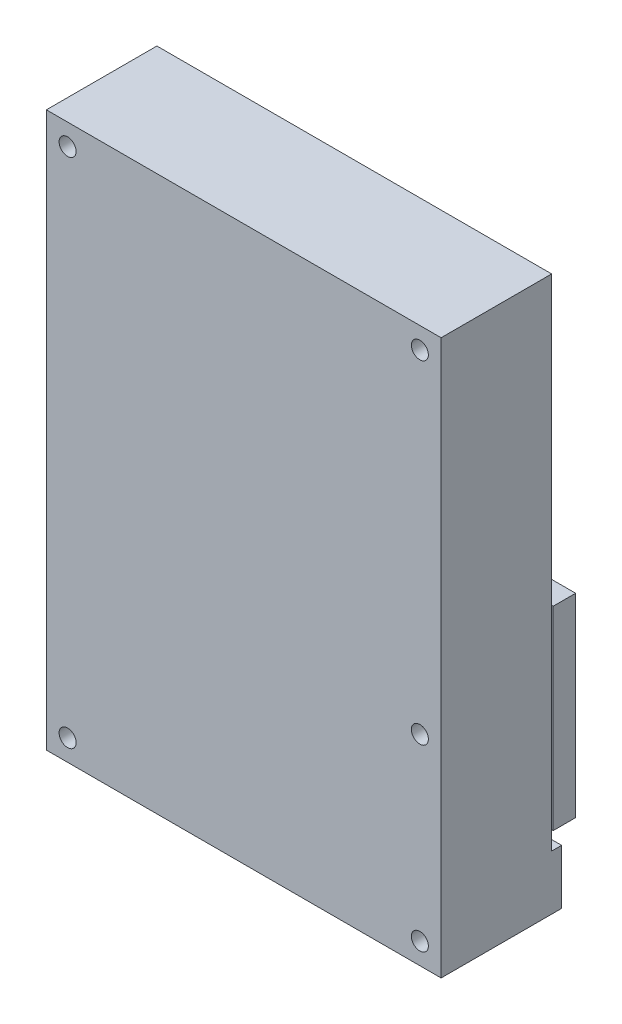
SolidWorks part; units mm, degrees
material "PCB"
ref_plane "Front Plane" through (0, 0, 0) normal (0, 0, 1) x (1, 0, 0)
ref_plane "Top Plane" through (0, 0, 0) normal (0, 1, 0) x (1, 0, 0)
ref_plane "Right Plane" through (0, 0, 0) normal (1, 0, 0) x (0, 0, -1)
sketch "Sketch1" plane through (0, 0, 0) normal (0, 0, 1) x (1, 0, 0)
  line L1 (-30.6623, 34.8708) -> (34.3377, 34.8708)
  line L2 (-30.6623, 34.8708) -> (-30.6623, -56.4292)
  line L3 (-30.6623, -56.4292) -> (34.3377, -56.4292)
  line L4 (34.3377, 34.8708) -> (34.3377, -56.4292)
  dimension "D1" = 65
  dimension "D2" = 91.3
extrude "Boss-Extrude2" add sketch "Sketch1" along normal blind 18.2
sketch "Sketch7" plane through (0, 0, 0) normal (0, 0, -1) x (-1, 0, 0)
  line L0 (-34.3377, -56.4292) -> (-34.3377, 34.8708) construction
  line L1 (30.6623, -56.4292) -> (-34.3377, -56.4292)
  line L2 (30.6623, -56.4292) -> (30.6623, -47.4292)
  line L3 (30.6623, -47.4292) -> (-34.3377, -47.4292)
  line L4 (-34.3377, -56.4292) -> (-34.3377, -47.4292)
  dimension "D1" = 9
sketch "Sketch12" plane through (0, 0, 0) normal (0, 0, -1) x (-1, 0, 0)
  line L1 (-34.3377, -56.4292) -> (30.6623, -56.4292)
  line L2 (-34.3377, -56.4292) -> (-34.3377, -47.4292)
  line L3 (-34.3377, -47.4292) -> (30.6623, -47.4292)
  line L4 (30.6623, -56.4292) -> (30.6623, -47.4292)
extrude "Boss-Extrude7" add sketch "Sketch12" along normal blind 1.64
sketch "Sketch13" plane through (0, -56.4292, 0) normal (0, -1, 0) x (1, 0, 0)
  line L0 (-30.6623, 18.2) -> (-30.6623, -1.64) construction
  line L1 (15.4377, 3.2) -> (-18.7623, 3.2)
  line L2 (15.4377, 3.2) -> (15.4377, 2.95)
  line L3 (15.4377, 2.95) -> (-18.7623, 2.95)
  line L4 (-18.7623, 3.2) -> (-18.7623, 2.95)
  line L6 (-30.6623, 18.2) -> (34.3377, 18.2) construction
  dimension "D1" = 11.9
  dimension "D2" = 34.2
  dimension "D3" = 0.25
  dimension "D4" = 15
extrude "Boss-Extrude8" add sketch "Sketch13" along normal blind 5.61
sketch "Sketch18" plane through (-18.7623, 0, 0) normal (-1, 0, 0) x (0, 0, 1)
  line L0 (2.95, -62.0392) -> (2.95, -56.4292) construction
  line L1 (3.2, -62.0392) -> (2.95, -62.0392) construction
  line L2 (3.2, -62.0392) -> (2.95, -62.0392)
  line L3 (-14.55, -62.0392) -> (-14.8, -62.0392)
  arc A0 (2.95, -62.0392) -> (-14.55, -62.0392) centre (-5.8, -62.0392) cw
  arc A1 (3.2, -62.0392) -> (-14.8, -62.0392) centre (-5.8, -62.0392) cw
  point P0 (-5.8, -62.0392)
  dimension "D3" = 8.75
  dimension "D1" = 8.75
  dimension "D2" = 0
extrude "Boss-Extrude13" add sketch "Sketch18" against normal blind 34.2
sketch "Sketch19" plane through (0, -62.0392, 0) normal (0, 1, 0) x (1, 0, 0)
  line L1 (-18.7623, 14.8) -> (15.4377, 14.8)
  line L2 (-18.7623, 14.8) -> (-18.7623, 14.55)
  line L3 (-18.7623, 14.55) -> (15.4377, 14.55)
  line L4 (15.4377, 14.8) -> (15.4377, 14.55)
extrude "Boss-Extrude14" add sketch "Sketch19" along normal blind 4.1
sketch "Sketch20" plane through (0, -57.9392, 0) normal (0, 1, 0) x (1, 0, 0)
  line L0 (-18.7623, 14.8) -> (-18.7623, 14.55) construction
  line L1 (-24.3623, 17.25) -> (21.0377, 17.25)
  line L2 (-24.3623, 17.25) -> (-24.3623, 13.55)
  line L3 (-24.3623, 13.55) -> (21.0377, 13.55)
  line L4 (21.0377, 17.25) -> (21.0377, 13.55)
  line L5 (15.4377, 14.8) -> (-18.7623, 14.8) construction
  line L6 (-18.7623, 14.55) -> (15.4377, 14.55) construction
  dimension "D1" = 5.6
  dimension "D2" = 45.4
  dimension "D3" = 2.45
  dimension "D4" = 1
extrude "Boss-Extrude15" add sketch "Sketch20" along normal blind 32
sketch "Sketch21" plane through (0, 0, 18.2) normal (0, 0, 1) x (1, 0, 0)
  line L0 (34.3377, -56.4292) -> (34.3377, 34.8708) construction
  line L1 (34.3377, 34.8708) -> (-30.6623, 34.8708) construction
  circle A0 centre (30.8377, 31.3708) radius 1.4
  dimension "D3" = 2.8
  dimension "D1" = 3.5
  dimension "D2" = 3.5
extrude "Cut-Extrude2" cut sketch "Sketch21" against normal blind 32
sketch "Sketch22" plane through (0, 0, 18.2) normal (0, 0, 1) x (1, 0, 0)
  line L0 (-30.6623, 34.8708) -> (-30.6623, -56.4292) construction
  line L1 (34.3377, 34.8708) -> (-30.6623, 34.8708) construction
  circle A0 centre (-27.1623, 31.3708) radius 1.4
  dimension "D1" = 2.8
  dimension "D2" = 3.5
  dimension "D3" = 3.5
extrude "Cut-Extrude3" cut sketch "Sketch22" against normal blind 61
sketch "Sketch23" plane through (0, 0, 18.2) normal (0, 0, 1) x (1, 0, 0)
  line L0 (-30.6623, -56.4292) -> (34.3377, -56.4292) construction
  line L2 (34.3377, -56.4292) -> (34.3377, 34.8708) construction
  circle A0 centre (30.8377, -52.9292) radius 1.4
  dimension "D1" = 3.5
  dimension "D2" = 2.8
  dimension "D3" = 3.5
extrude "Cut-Extrude4" cut sketch "Sketch23" against normal blind 61
sketch "Sketch24" plane through (0, 0, 18.2) normal (0, 0, 1) x (1, 0, 0)
  line L0 (-30.6623, 34.8708) -> (-30.6623, -56.4292) construction
  line L1 (-30.6623, -56.4292) -> (34.3377, -56.4292) construction
  circle A0 centre (-27.1623, -52.9292) radius 1.4
  dimension "D1" = 2.8
  dimension "D2" = 3.5
  dimension "D3" = 3.5
extrude "Cut-Extrude5" cut sketch "Sketch24" against normal blind 61
sketch "Sketch25" plane through (0, 0, -17.25) normal (0, 0, -1) x (-1, 0, 0)
  line L0 (-21.0377, -25.9392) -> (24.3623, -25.9392) construction
  line L1 (24.3623, -25.9392) -> (24.3623, -57.9392) construction
  circle A0 centre (21.6623, -39.9392) radius 1.3
  dimension "D1" = 2.6
  dimension "D2" = 14
  dimension "D3" = 2.7
extrude "Cut-Extrude6" cut sketch "Sketch25" against normal blind 10
sketch "Sketch26" plane through (0, 0, -17.25) normal (0, 0, -1) x (-1, 0, 0)
  line L0 (-21.0377, -25.9392) -> (24.3623, -25.9392) construction
  line L1 (-21.0377, -25.9392) -> (-21.0377, -57.9392) construction
  circle A0 centre (-18.3377, -39.9392) radius 1.3
  dimension "D1" = 2.6
  dimension "D2" = 14
  dimension "D3" = 2.7
extrude "Cut-Extrude7" cut sketch "Sketch26" against normal blind 10
sketch "Sketch27" plane through (0, 0, 18.2) normal (0, 0, 1) x (1, 0, 0)
  line L0 (34.3377, -56.4292) -> (34.3377, 34.8708) construction
  circle A0 centre (30.8377, -23.4292) radius 1.4
  circle A1 centre (30.8377, -52.9292) radius 1.4 construction
  dimension "D1" = 2.8
  dimension "D2" = 3.5
  dimension "D3" = 29.5
extrude "Cut-Extrude9" cut sketch "Sketch27" against normal blind 1500
sketch "Sketch29" plane through (-30.6623, 0, 0) normal (-1, 0, 0) x (0, 0, 1)
  line L0 (6.5, -56.4292) -> (6.5, 34.8708)
  line L1 (18.2, -56.4292) -> (-1.64, -56.4292) construction
  line L2 (18.2, 34.8708) -> (0, 34.8708) construction
  line L3 (4.8, -56.4292) -> (4.8, 34.8708)
  line L4 (18.2, 34.8708) -> (18.2, -56.4292) construction
  dimension "D1" = 11.7
  dimension "D2" = 1.7
sketch "Sketch30" plane through (0, 0, -17.25) normal (0, 0, -1) x (-1, 0, 0)
  line L0 (-21.0377, -25.9392) -> (-21.0377, -57.9392) construction
  line L1 (-21.0377, -25.9392) -> (24.3623, -25.9392) construction
  point P0 (1.6623, -39.9392)
  dimension "D1" = 22.7
  dimension "D2" = 14
ref_axis "Axis1" through (-1.6623, -39.9392, -17.25) along (0, 0, -1)
